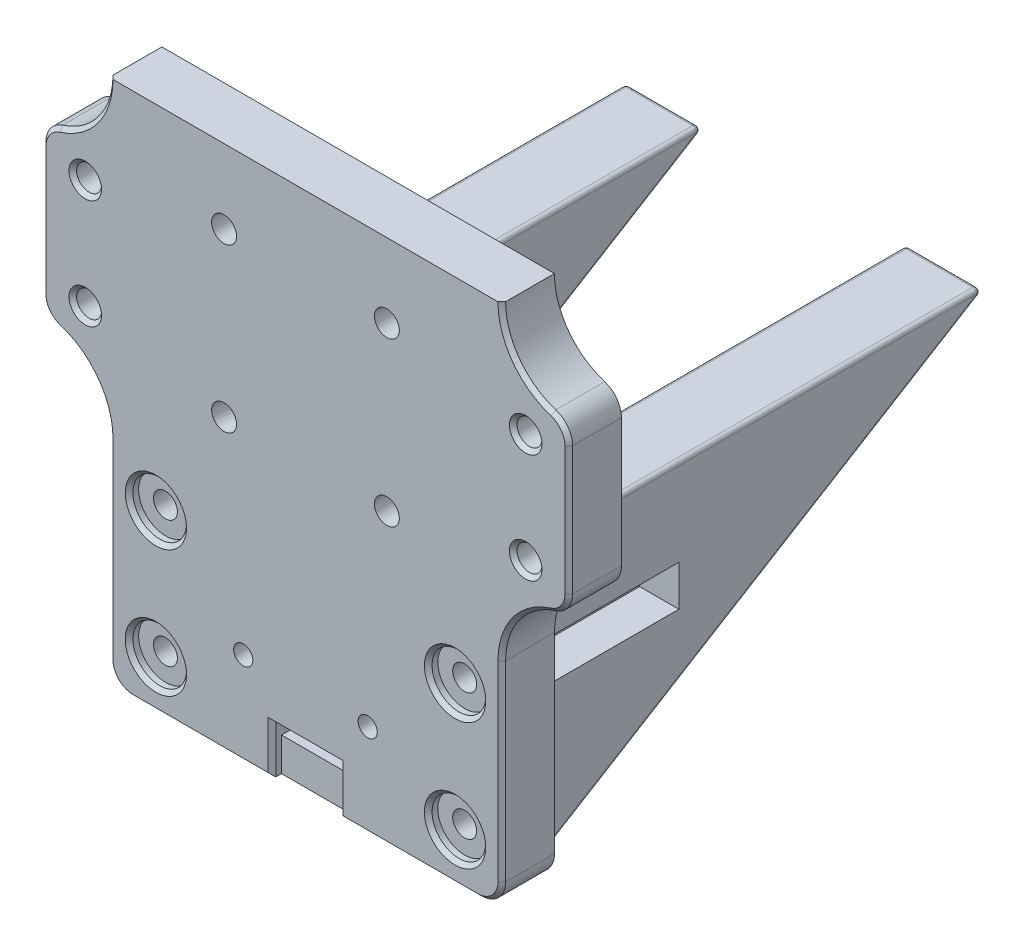
SolidWorks part; units mm, degrees
ref_plane "Front Plane" through (0, 0, 0) normal (0, 0, 1) x (1, 0, 0)
ref_plane "Top Plane" through (0, 0, 0) normal (0, 1, 0) x (1, 0, 0)
ref_plane "Right Plane" through (0, 0, 0) normal (1, 0, 0) x (0, 0, -1)
sketch "Sketch1" plane through (0, 0, 0) normal (0, 0, 1) x (1, 0, 0)
  line L1 (-31.25, -41) -> (31.25, -41) construction
  line L2 (-31.25, -41) -> (-31.25, 41) construction
  line L3 (-31.25, 41) -> (31.25, 41) construction
  line L4 (31.25, -41) -> (31.25, 41) construction
  line L5 (-31.25, -41) -> (31.25, 41) construction
  line L6 (-31.25, 41) -> (31.25, -41) construction
  line L7 (-41, -77.5) -> (41, -77.5)
  line L8 (-41, -77.5) -> (-41, 77.5)
  line L9 (-41, 77.5) -> (41, 77.5)
  line L10 (41, -77.5) -> (41, 77.5)
  line L11 (-41, -77.5) -> (41, 77.5) construction
  line L12 (-41, 77.5) -> (41, -77.5) construction
  line L13 (-31.25, -67.5) -> (31.25, -67.5) construction
  line L14 (-31.25, -67.5) -> (-31.25, 67.5) construction
  line L15 (-31.25, 67.5) -> (31.25, 67.5) construction
  line L16 (31.25, -67.5) -> (31.25, 67.5) construction
  line L17 (-31.25, -67.5) -> (31.25, 67.5) construction
  line L18 (-31.25, 67.5) -> (31.25, -67.5) construction
  circle A0 centre (31.25, 41) radius 2.5
  circle A1 centre (31.25, -41) radius 2.5
  circle A2 centre (-31.25, -41) radius 2.5
  circle A3 centre (-31.25, 41) radius 2.5
  circle A4 centre (-31.25, 67.5) radius 2.5
  circle A5 centre (31.25, 67.5) radius 2.5
  circle A6 centre (31.25, -67.5) radius 2.5
  circle A7 centre (-31.25, -67.5) radius 2.5
  point P0 (0, 0)
  point P10 (0, 0)
  point P15 (0, 0)
  dimension "D3" = 135
  dimension "D4" = 5
  dimension "D7" = 5
  dimension "D1" = 62.5
  dimension "D2" = 82
  dimension "D5" = 155
  dimension "D6" = 82
extrude "Boss-Extrude1" add sketch "Sketch1" along normal blind 11
sketch "Sketch6" plane through (0, 0, 11) normal (0, 0, 1) x (1, 0, 0)
  line L1 (-55, -18.4) -> (55, -18.4)
  line L2 (-55, -18.4) -> (-55, 18.4)
  line L3 (-55, 18.4) -> (55, 18.4)
  line L4 (55, -18.4) -> (55, 18.4)
  line L5 (-55, -18.4) -> (55, 18.4) construction
  line L6 (-55, 18.4) -> (55, -18.4) construction
  point P0 (0, 0)
  dimension "D1" = 36.8
  dimension "D2" = 110
extrude "Boss-Extrude4" add sketch "Sketch6" against normal up to surface (11 mm away) up to face at (33.75, -67.5, 0)
sketch "Sketch8" plane through (0, 0, 0) normal (0, 0, -1) x (-1, 0, 0)
  line L0 (-41, -18.4) -> (-55, -18.4) construction
  line L1 (-21, -19.4) -> (21, -19.4)
  line L2 (-21, -19.4) -> (-21, -57.4)
  line L3 (-21, -57.4) -> (21, -57.4)
  line L4 (21, -19.4) -> (21, -57.4)
  point P6 (0, -19.4)
  dimension "D1" = 38
  dimension "D2" = 42
  dimension "D3" = 1
sketch "Sketch9" plane through (0, 0, 0) normal (0, 0, -1) x (-1, 0, 0)
  line L0 (-41, 77.5) -> (41, 77.5) construction
  line L1 (-7, 70.5) -> (7, 70.5)
  line L2 (-7, 70.5) -> (-7, 67.5)
  line L3 (-7, 67.5) -> (7, 67.5)
  line L4 (7, 70.5) -> (7, 67.5)
  line L5 (-7, 70.5) -> (7, 67.5) construction
  line L6 (-7, 67.5) -> (7, 70.5) construction
  line L7 (-7, -67.5) -> (7, -67.5)
  line L8 (-7, -67.5) -> (-7, -70.5)
  line L9 (-7, -70.5) -> (7, -70.5)
  line L10 (7, -67.5) -> (7, -70.5)
  line L11 (-7, -67.5) -> (7, -70.5) construction
  line L12 (-7, -70.5) -> (7, -67.5) construction
  line L13 (41, -77.5) -> (-41, -77.5) construction
  point P0 (0, 69)
  point P5 (0, -69)
  dimension "D1" = 3
  dimension "D2" = 14
  dimension "D3" = 3
  dimension "D4" = 14
  dimension "D5" = 7
  dimension "D6" = 7
extrude "Cut-Extrude2" cut sketch "Sketch9" against normal through all
fillet "Fillet1" radius 5 8 edges at (41, -77.5, 5.5) (-41, -77.5, 5.5) (-55, -18.4, 5.5) (-55, 18.4, 5.5) (-41, 77.5, 5.5) (55, 18.4, 5.5) (55, -18.4, 5.5) (41, 77.5, 5.5)
sketch "Sketch10" plane through (0, 0, 0) normal (0, 0, -1) x (-1, 0, 0)
  line L0 (-50, 18.4) -> (-41, 18.4) construction
  line L1 (-41, -18.4) -> (-50, -18.4) construction
  line L2 (0, 48.025) -> (0, -34.9364) construction
  circle A0 centre (-46, 11.4) radius 2.6
  circle A1 centre (-46, -11.4) radius 2.6
  circle A2 centre (46, -11.4) radius 2.6
  circle A3 centre (46, 11.4) radius 2.6
  dimension "D1" = 5.2
  dimension "D2" = 5.2
  dimension "D3" = 46
  dimension "D4" = 7
  dimension "D5" = 7
extrude "Cut-Extrude3" cut sketch "Sketch10" against normal through all
fillet "Fillet3" radius 15 4 edges at (41, -18.4, 5.5) (-41, -18.4, 5.5) (-41, 18.4, 5.5) (41, 18.4, 5.5)
sketch "Sketch14" plane through (0, 0, 11) normal (0, 0, 1) x (1, 0, 0)
  circle A0 centre (31.25, -41) radius 5.6
  circle A1 centre (31.25, -67.5) radius 5.6
  circle A2 centre (31.25, 41) radius 5.6
  circle A3 centre (31.25, 67.5) radius 5.6
  circle A4 centre (-31.25, 67.5) radius 5.6
  circle A5 centre (-31.25, 41) radius 5.6
  circle A6 centre (-31.25, -41) radius 5.6
  circle A7 centre (-31.25, -67.5) radius 5.6
  dimension "D1" = 11.2
extrude "Cut-Extrude7" cut sketch "Sketch14" against normal blind 2
sketch "Sketch18" plane through (0, 0, 11) normal (0, 0, 1) x (1, 0, 0)
  line L0 (36, 77.5) -> (-36, 77.5) construction
  line L1 (-7, 70.5) -> (7, 70.5)
  line L2 (-7, 70.5) -> (-7, 77.5)
  line L3 (-7, 77.5) -> (7, 77.5)
  line L4 (7, 70.5) -> (7, 77.5)
  line L5 (-36, -77.5) -> (36, -77.5) construction
  line L6 (-7, -70.5) -> (7, -70.5)
  line L7 (-7, -70.5) -> (-7, -77.5)
  line L8 (-7, -77.5) -> (7, -77.5)
  line L9 (7, -70.5) -> (7, -77.5)
  line L10 (7, -67.5) -> (7, -70.5) construction
extrude "Cut-Extrude10" cut sketch "Sketch18" against normal blind 2
sketch "Sketch16" plane through (0, 0, 0) normal (1, 0, 0) x (0, 0, -1)
  line L0 (0, -18.5) -> (0, -76.5)
  line L1 (0, -13.4) -> (0, 13.4) construction
  line L2 (0, -72.5) -> (0, -32.4788) construction
  line L3 (0, -76.5) -> (95, -18.5)
  line L4 (95, -18.5) -> (0, -18.5)
  line L5 (0, -77.5) -> (-11, -77.5) construction
  line L6 (0, -77.5) -> (0, -72.5) construction
  dimension "D1" = 59
  dimension "D2" = 95
  dimension "D3" = 1
extrude "Boss-Extrude5" add sketch "Sketch16" along normal mid plane 74
extrude "Cut-Extrude8" cut sketch "Sketch16<2>" against normal mid plane 43
sketch "Sketch16<2>" plane through (0, 0, 0) normal (1, 0, 0) x (0, 0, -1) same geometry as "Sketch16"
sketch "Sketch17" plane through (0, 0, 0) normal (0, 0, -1) x (-1, 0, 0)
  line L0 (-33.7037, -36.75) -> (-37, -36.75)
  line L1 (-28.7963, -36.75) -> (-33.7037, -36.75)
  line L2 (-33.7037, -36.75) -> (-36.1575, -41)
  line L3 (-36.1575, -41) -> (-33.7037, -45.25)
  line L4 (-33.7037, -45.25) -> (-28.7963, -45.25)
  line L5 (-28.7963, -45.25) -> (-26.3425, -41)
  line L6 (-26.3425, -41) -> (-28.7963, -36.75)
  line L7 (-28.7963, -63.25) -> (-33.7037, -63.25)
  line L8 (-33.7037, -63.25) -> (-36.1575, -67.5)
  line L9 (-36.1575, -67.5) -> (-33.7037, -71.75)
  line L10 (-33.7037, -71.75) -> (-28.7963, -71.75)
  line L11 (-28.7963, -71.75) -> (-26.3425, -67.5)
  line L12 (-26.3425, -67.5) -> (-28.7963, -63.25)
  line L13 (33.7037, -63.25) -> (28.7963, -63.25)
  line L14 (28.7963, -63.25) -> (26.3425, -67.5)
  line L15 (26.3425, -67.5) -> (28.7963, -71.75)
  line L16 (28.7963, -71.75) -> (33.7037, -71.75)
  line L17 (33.7037, -71.75) -> (36.1575, -67.5)
  line L18 (36.1575, -67.5) -> (33.7037, -63.25)
  line L19 (33.7037, -36.75) -> (28.7963, -36.75)
  line L20 (28.7963, -36.75) -> (26.3425, -41)
  line L21 (26.3425, -41) -> (28.7963, -45.25)
  line L22 (28.7963, -45.25) -> (33.7037, -45.25)
  line L23 (33.7037, -45.25) -> (36.1575, -41)
  line L24 (36.1575, -41) -> (33.7037, -36.75)
  line L25 (-37, -18.5) -> (-37, -76.5) construction
  line L26 (-37, -36.75) -> (-37, -45.25)
  line L28 (-37, -76.5) -> (-37, -18.5) construction
  line L29 (-37, -45.25) -> (-33.7037, -45.25)
  line L30 (33.7037, -36.75) -> (37, -36.75)
  line L31 (37, -18.5) -> (37, -76.5) construction
  line L32 (37, -36.75) -> (37, -45.25)
  line L33 (37, -45.25) -> (33.7037, -45.25)
  circle A4 centre (-31.25, -41) radius 4.25 construction
  circle A5 centre (-31.25, -67.5) radius 4.25 construction
  circle A6 centre (31.25, -67.5) radius 4.25 construction
  circle A7 centre (31.25, -41) radius 4.25 construction
  line M3 (-37, -76.5) -> (-37, -18.5)
  line M8 (37, -18.5) -> (37, -76.5)
  dimension "D1" = 8.5
chamfer "Chamfer2" distance 0.8 angle 45 40 edges at (-39.5355, -76.0355, 11) (-41, -52.4894, 11) (-54.0311, -16.358, 11) (-55, 0, 11) (-54.0311, 16.358, 11) (-41, 52.4894, 11) (-39.5355, 76.0355, 11) (-21.5, 77.5, 11) (21.5, 77.5, 11) (39.5355, 76.0355, 11) (41, 52.4894, 11) (54.0311, 16.358, 11) (55, 0, 11) (54.0311, -16.358, 11) (41, -52.4894, 11) (39.5355, -76.0355, 11) (-21.5, -77.5, 11) (21.5, -77.5, 11) (7, -72.5, 11) (0, -67.5, 11) (-7, -72.5, 11) (7, 72.5, 11) (-7, 72.5, 11) (0, 67.5, 11) (43.4, 11.4, 11) (43.4, -11.4, 11) (-43.4, -11.4, 11) (-43.4, 11.4, 11) (36.85, -41, 11) (-25.65, -67.5, 11) (-25.65, -41, 11) (-25.65, 41, 11) (-25.65, 67.5, 11) (36.85, 67.5, 11) (36.85, 41, 11) (36.85, -67.5, 11) (-43.9066, -23.6047, 11) (-43.9066, 23.6047, 11) (43.9066, 23.6047, 11) (43.9066, -23.6047, 11)
sketch "Sketch11" plane through (0, 0, 0) normal (0, 0, -1) x (-1, 0, 0)
  line L0 (0, 0) -> (0, -47.0529) construction
  circle A0 centre (-13, -58) radius 2
  circle A1 centre (13, -58) radius 2
  dimension "D3" = 4
  dimension "D1" = 58
  dimension "D2" = 13
extrude "Cut-Extrude4" cut sketch "Sketch11" against normal through all
sketch "Sketch12" plane through (0, 0, 0) normal (0, 0, -1) x (-1, 0, 0)
  line L1 (14.6166, -55.2) -> (11.3834, -55.2)
  line L2 (11.3834, -55.2) -> (9.7668, -58)
  line L3 (9.7668, -58) -> (11.3834, -60.8)
  line L4 (11.3834, -60.8) -> (14.6166, -60.8)
  line L5 (14.6166, -60.8) -> (16.2332, -58)
  line L6 (16.2332, -58) -> (14.6166, -55.2)
  line L7 (-11.3834, -55.2) -> (-14.6166, -55.2)
  line L8 (-14.6166, -55.2) -> (-16.2332, -58)
  line L9 (-16.2332, -58) -> (-14.6166, -60.8)
  line L10 (-14.6166, -60.8) -> (-11.3834, -60.8)
  line L11 (-11.3834, -60.8) -> (-9.7668, -58)
  line L12 (-9.7668, -58) -> (-11.3834, -55.2)
  circle A0 centre (13, -58) radius 2.8 construction
  circle A1 centre (-13, -58) radius 2.8 construction
  dimension "D1" = 5.6
  dimension "D2" = 5.6
extrude "Cut-Extrude5" cut sketch "Sketch12" against normal blind 2.6
sketch "Sketch13" plane through (0, 0, 0) normal (0, 0, -1) x (-1, 0, 0)
  line L5 (-9.525, -49) -> (9.525, -49)
  line L6 (-9.525, -49) -> (-9.525, 61)
  line L7 (-42.5, -9.525) -> (42.5, -9.525)
  line L8 (-42.5, -9.525) -> (-42.5, 9.525)
  line L9 (-42.5, 9.525) -> (42.5, 9.525)
  line L10 (42.5, -9.525) -> (42.5, 9.525)
  line L11 (-42.5, -9.525) -> (42.5, 9.525) construction
  line L12 (-42.5, 9.525) -> (42.5, -9.525) construction
  line L13 (-9.525, 61) -> (9.525, 61)
  line L14 (9.525, -49) -> (9.525, 61)
  line L15 (-9.525, -49) -> (9.525, 61) construction
  line L16 (-9.525, 61) -> (9.525, -49) construction
  point P0 (0, 0)
  point P1 (0, 6)
  point P6 (0, 0)
  dimension "D1" = 19.05
  dimension "D2" = 85
  dimension "D3" = 110
  dimension "D4" = 6
extrude "Cut-Extrude9" cut sketch "Sketch17" along normal blind 30 contours L29 L3 L2 L0 M3 | L33 L30 L24 L23 M8 | L23 L24 L19 L20 L21 L22 | L17 L18 L13 L14 L15 L16 | L11 L12 L7 L8 L9 L10 | L5 L6 L1 L2 L3 L4 region at (35.0096, -38.8294, 0) region at (31.25, -41, 0) region at (31.25, -67.5, 0) region at (-31.25, -67.5, 0) region at (-31.25, -41, 0) region at (-35.3519, -36.8412, 0)
fillet "Fillet4" radius 0.8 10 edges at (-29.25, -18.5, -95) (29.25, -18.5, -95) (-37, -18.5, -47.5) (-37, -47.5, -47.5) (-21.5, -47.5, -47.5) (-21.5, -18.5, -47.5) (21.5, -18.5, -47.5) (37, -18.5, -47.5) (21.5, -47.5, -47.5) (37, -47.5, -47.5)
sketch "Croquis1" plane through (0, 0, 0) normal (0, 0, -1) x (-1, 0, 0)
  line L0 (-41, 32.4788) -> (41, 32.4788)
  line L1 (41, 32.4788) -> (41, 72.5)
  line L2 (-41, 32.4788) -> (-41, 72.5)
  line L3 (-36, 77.5) -> (36, 77.5)
  circle A0 centre (-36, 72.5) radius 5
  circle A1 centre (36, 72.5) radius 5
extrude "Cortar-Extruir1" cut sketch "Croquis1" against normal blind 11 contours A1 L3 A0 L2 L0 L1 | A1 | A0 region at (0, 54.1437, 0) region at (36, 72.5, 0) region at (-36, 72.5, 0)
sketch "Croquis2" plane through (0, 0, 0) normal (0, 0, -1) x (-1, 0, 0)
  line L0 (-46, 11.4) -> (46, -11.4)
  line L1 (-46, -11.4) -> (46, 11.4)
  line L3 (-17, -17) -> (17, -17)
  line L4 (-17, -17) -> (-17, 17)
  line L5 (-17, 17) -> (17, 17)
  line L6 (17, -17) -> (17, 17)
  line L7 (-17, -17) -> (17, 17) construction
  line L8 (-17, 17) -> (17, -17) construction
  circle A0 centre (-17, 17) radius 2.6
  circle A1 centre (17, 17) radius 2.6
  circle A2 centre (-17, -17) radius 2.6
  circle A3 centre (17, -17) radius 2.6
  point P8 (0, 0)
  dimension "D1" = 34
  dimension "D2" = 34
extrude "Cortar-Extruir2" cut sketch "Croquis2" against normal blind 11 contours L6 A1 L5 | L3 A3 L6 | L6 A3 L3 | L3 A2 L4 | L4 A2 L3 | L5 A0 L4 | L4 A0 L5 | L5 A1 L6 region at (17.3678, 17.3678, 0) region at (15.8965, 15.8965, 0) region at (15.8965, -15.8965, 0) region at (17.3678, -17.3678, 0) region at (-17.3678, -17.3678, 0) region at (-15.8965, -15.8965, 0) region at (-15.8965, 15.8965, 0) region at (-17.3678, 17.3678, 0)
